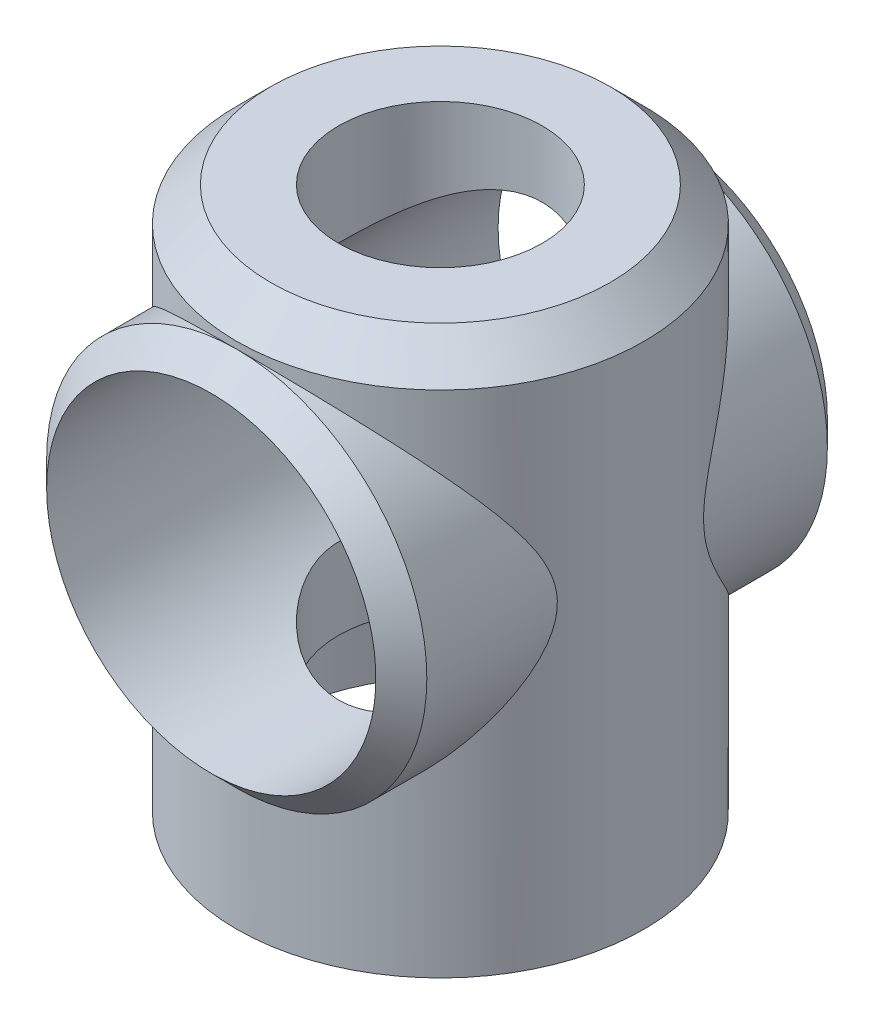
SolidWorks part; units mm, degrees
material "Custom Plastic"
ref_plane "Front Plane" through (0, 0, 0) normal (0, 0, 1) x (1, 0, 0)
ref_plane "Top Plane" through (0, 0, 0) normal (0, 1, 0) x (1, 0, 0)
ref_plane "Right Plane" through (0, 0, 0) normal (1, 0, 0) x (0, 0, -1)
ref_plane "Plane2" through (0, 0, 17) normal (0, 0, 1) x (1, 0, 0)
sketch "Sketch4" plane through (0, 0, 0) normal (0, 1, 0) x (1, 0, 0)
  circle A0 centre (0, 0) radius 15
  dimension "D1" = 30
extrude "Boss-Extrude3" add sketch "Sketch4" along normal blind 40
sketch "Sketch5" plane through (0, 40, 0) normal (0, 1, 0) x (1, 0, 0)
  circle A0 centre (0, 0) radius 7.5
  dimension "D1" = 15
extrude "Cut-Extrude2" cut sketch "Sketch5" against normal through all
sketch "Sketch6" plane through (0, 0, 0) normal (0, 0, 1) x (1, 0, 0)
  line L0 (15, 23) -> (-15, 23) construction
  line L3 (15, 0) -> (15, 40) construction
  line L4 (-15, 40) -> (-15, 0) construction
  line L5 (15, 40) -> (-15, 40) construction
  circle A0 centre (0, 23) radius 12.125
  point P12 (0, 23)
  dimension "D1" = 24.25
  dimension "D2" = 17
extrude "Cut-Extrude3" cut sketch "Sketch6" along normal through all both and the other way through all
sketch "Sketch7" plane through (0, 0, 17) normal (0, 0, 1) x (1, 0, 0)
  circle A0 centre (0, 23) radius 12.125 construction
  circle A1 centre (0, 23) radius 12.125
  circle A2 centre (0, 23) radius 14
  dimension "D1" = 28
extrude "Boss-Extrude5" add sketch "Sketch7" against normal up to surface (8.1691 mm away) up to face at (0, 40, 15)
mirror "Mirror2" about plane through (0, 0, 0) normal (0, 0, 1) of "Boss-Extrude5"
chamfer "Chamfer2" distance 2 angle 45 1 edges at (14, 23, 17)
chamfer "Chamfer3" distance 2.5 angle 45 1 edges at (0, 40, 15)
sketch "Sketch8" plane through (0, 0, 0) normal (0, -1, 0) x (1, 0, 0)
  circle A0 centre (0, 0) radius 12.1
  dimension "D1" = 24.2
extrude "Cut-Extrude4" cut sketch "Sketch8" against normal blind 7.5 and the other way through all contours A0
chamfer "Chamfer4" distance 2.5 angle 45 1 edges at (14, 23, -17)
